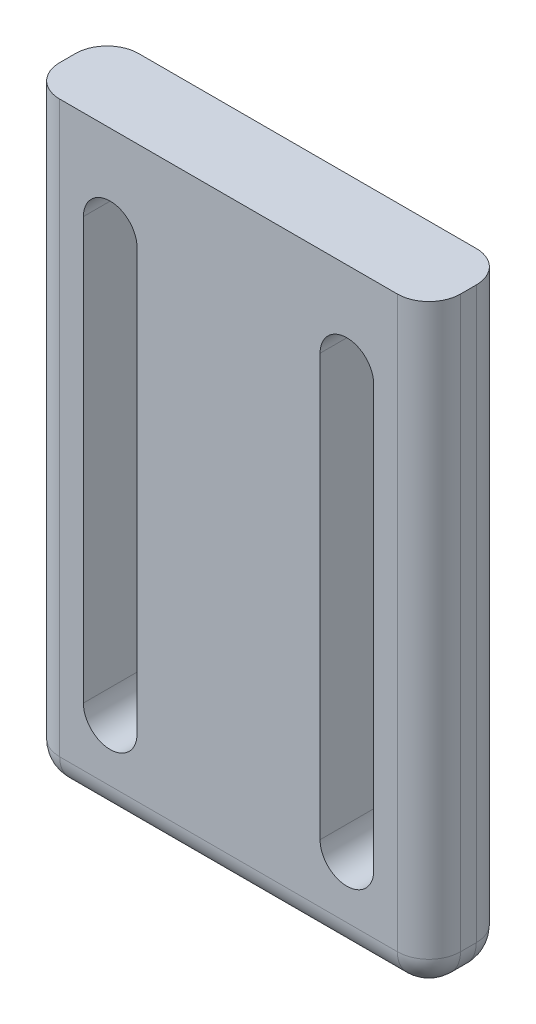
SolidWorks part; units mm, degrees
ref_plane "Front Plane" through (0, 0, 0) normal (0, 0, 1) x (1, 0, 0)
ref_plane "Top Plane" through (0, 0, 0) normal (0, 1, 0) x (1, 0, 0)
ref_plane "Right Plane" through (0, 0, 0) normal (1, 0, 0) x (0, 0, -1)
sketch "Sketch1" plane through (0, 0, 0) normal (0, 0, 1) x (1, 0, 0)
  line L1 (-12.7, 19.05) -> (12.7, 19.05)
  line L2 (-12.7, 19.05) -> (-12.7, -19.05)
  line L3 (-12.7, -19.05) -> (12.7, -19.05)
  line L4 (12.7, 19.05) -> (12.7, -19.05)
  line L5 (-12.7, 19.05) -> (12.7, -19.05) construction
  line L6 (-12.7, -19.05) -> (12.7, 19.05) construction
  point P0 (0, 0)
  dimension "D1" = 25.4
  dimension "D2" = 38.1
extrude "Boss-Extrude1" add sketch "Sketch1" along normal blind 5
sketch "Sketch2" plane through (0, 0, 5) normal (0, 0, 1) x (1, 0, 0)
  line L0 (0, -19.05) -> (0, 19.05) construction
  line L1 (12.7, 19.05) -> (-12.7, 19.05) construction
  line L2 (-7.5, 0) -> (7.5, 0) construction
  line L3 (9.2, 15.05) -> (5.8, 15.05)
  line L4 (-9.2, -15.05) -> (-5.8, -15.05)
  line L5 (-9.2, -15.05) -> (-9.2, 15.05)
  line L6 (-9.2, 15.05) -> (-5.8, 15.05)
  line L7 (-5.8, -15.05) -> (-5.8, 15.05)
  line L8 (-9.2, -15.05) -> (-5.8, 15.05) construction
  line L9 (-9.2, 15.05) -> (-5.8, -15.05) construction
  line L10 (5.8, -15.05) -> (5.8, 15.05)
  line L11 (9.2, -15.05) -> (5.8, -15.05)
  line L12 (9.2, -15.05) -> (9.2, 15.05)
  point P6 (0, 0)
  point P10 (0, 0)
  dimension "D1" = 15
  dimension "D2" = 3.4
  dimension "D3" = 30.1
extrude "Cut-Extrude1" cut sketch "Sketch2" against normal through all
fillet "Fillet1" 2 edges at (-9.2, 15.05, 2.5) (-5.8, 15.05, 2.5) type full round first side face at (-9.2, 0, 2.5) second side face at (-5.8, 0, 2.5) middle face at (-7.5, 15.05, 2.5)
fillet "Fillet2" 2 edges at (-9.2, -15.05, 2.5) (-5.8, -15.05, 2.5) type full round first side face at (-9.2, -0.85, 2.5) second side face at (-5.8, -0.85, 2.5) middle face at (-7.5, -15.05, 2.5)
fillet "Fillet3" 2 edges at (5.8, 15.05, 2.5) (9.2, 15.05, 2.5) type full round first side face at (5.8, 0, 2.5) second side face at (9.2, 0, 2.5) middle face at (7.5, 15.05, 2.5)
fillet "Fillet4" 2 edges at (5.8, -15.05, 2.5) (9.2, -15.05, 2.5) type full round first side face at (5.8, -0.85, 2.5) second side face at (9.2, -0.85, 2.5) middle face at (7.5, -15.05, 2.5)
fillet "Fillet5" radius 2 8 edges at (12.7, 0, 0) (12.7, 0, 5) (-12.7, 0, 0) (-12.7, 0, 5) (0, -19.05, 0) (0, -19.05, 5) (12.7, -19.05, 2.5) (-12.7, -19.05, 2.5)
sketch "Sketch3" plane through (0, 19.05, 0) normal (0, 1, 0) x (1, 0, 0)
  line L0 (0, 0) -> (0, -5) construction
  line L1 (10.7, -5) -> (-10.7, -5) construction
  circle A0 centre (0, -2.5) radius 1.0065
